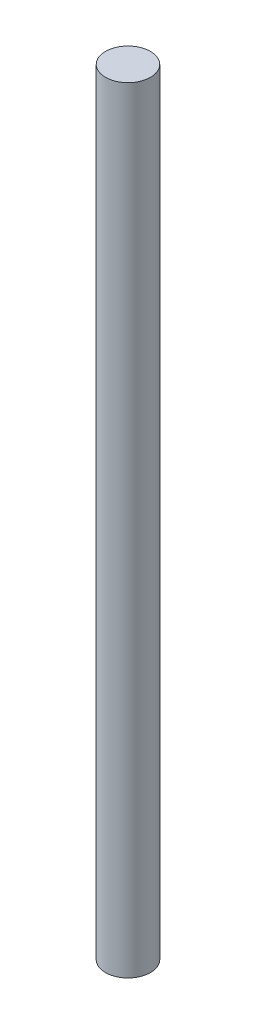
SolidWorks part; units mm, degrees
ref_plane "前视基准面" through (0, 0, 0) normal (0, 0, 1) x (1, 0, 0)
ref_plane "上视基准面" through (0, 0, 0) normal (0, 1, 0) x (1, 0, 0)
ref_plane "右视基准面" through (0, 0, 0) normal (1, 0, 0) x (0, 0, -1)
sketch "草图1" plane through (0, 0, 0) normal (0, 1, 0) x (1, 0, 0)
  circle A0 centre (0, 0) radius 1
  dimension "D1" = 2
extrude "凸台-拉伸1" add sketch "草图1" along normal blind 34.5
